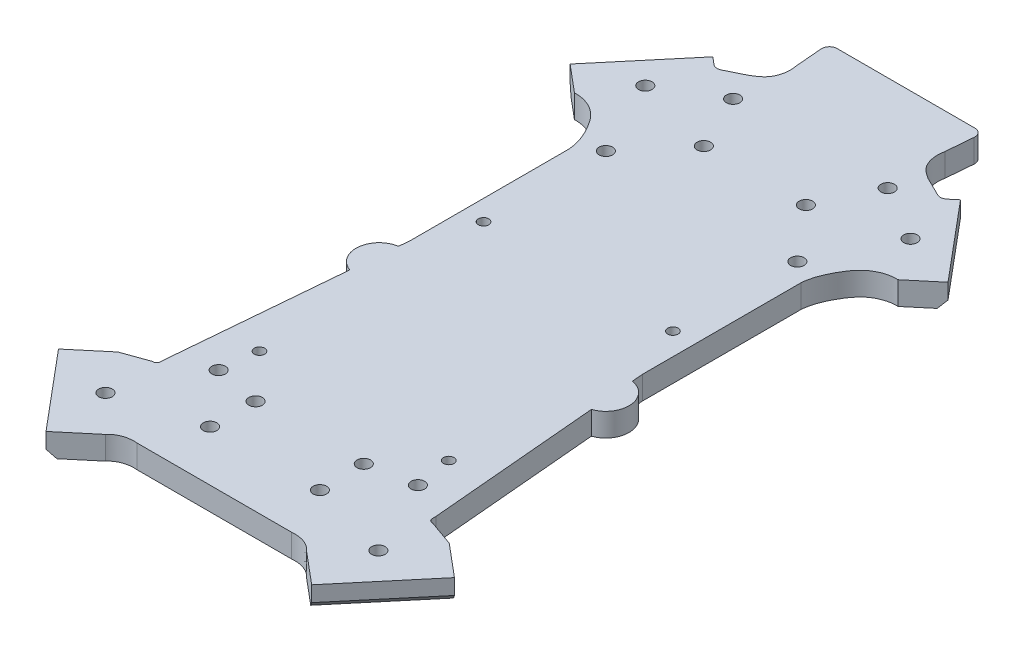
SolidWorks part; units mm, degrees
ref_plane "Front Plane" through (0, 0, 0) normal (0, 0, 1) x (1, 0, 0)
ref_plane "Top Plane" through (0, 0, 0) normal (0, 1, 0) x (1, 0, 0)
ref_plane "Right Plane" through (0, 0, 0) normal (1, 0, 0) x (0, 0, -1)
sketch "Sketch1" plane through (0, 0, 0) normal (0, 1, 0) x (1, 0, 0)
  line L1 (0, 0) -> (200, 0)
  line L2 (0, 0) -> (0, 200)
  line L3 (0, 200) -> (200, 200)
  line L4 (200, 0) -> (200, 200)
  dimension "D1" = 200
  dimension "D2" = 200
extrude "Boss-Extrude1" add sketch "Sketch1" along normal blind 6
sketch "Sketch2" plane through (0, 0, 0) normal (0, -1, 0) x (1, 0, 0)
  line L0 (143.2063, -38.4743) -> (139.3486, -82.5678)
  line L2 (138.3335, -94.1709) -> (138.0819, -97.0459)
  line L3 (138.0819, -97.0459) -> (138.0819, -138.1223)
  line L5 (128.0819, -16.2435) -> (88.0819, -16.2435)
  line L8 (72.9576, -38.4743) -> (76.8153, -82.5678)
  line L10 (77.8304, -94.1709) -> (78.0819, -97.0459)
  line L11 (78.0819, -97.0459) -> (78.0819, -138.1223)
  line L12 (136.0689, -175.4633) -> (131.2216, -177.8581)
  line L14 (127.295, -186.0703) -> (127.8892, -193.0744)
  line L15 (125.8964, -195.2435) -> (90.2675, -195.2435)
  line L16 (108.0819, -195.2435) -> (108.0819, -160.9159) construction
  line L17 (88.8688, -186.0703) -> (88.2746, -193.0744)
  line L18 (80.095, -175.4633) -> (84.9422, -177.8581)
  line L21 (71.8743, -36.5483) -> (65.2141, -34.1729)
  line L22 (65.2141, -34.1729) -> (56.8447, -27.1502)
  line L23 (56.8447, -27.1502) -> (73.7024, -7.0599)
  line L25 (73.7024, -7.0599) -> (82.0719, -14.0827)
  line L30 (66.2141, -151.3141) -> (63.7367, -153.3929)
  line L32 (63.7367, -153.3929) -> (59.1776, -157.2184)
  line L33 (59.1776, -157.2184) -> (76.0353, -177.3087)
  line L35 (76.0353, -177.3087) -> (77.9235, -175.7243)
  line L37 (142.4614, -7.0599) -> (134.092, -14.0827)
  line L38 (159.3191, -27.1502) -> (142.4614, -7.0599)
  line L39 (150.9497, -34.1729) -> (159.3191, -27.1502)
  line L40 (144.2896, -36.5483) -> (150.9497, -34.1729)
  line L45 (149.9497, -151.3141) -> (152.4271, -153.3929)
  line L46 (152.4271, -153.3929) -> (156.9863, -157.2184)
  line L47 (156.9863, -157.2184) -> (140.1285, -177.3087)
  line L48 (140.1285, -177.3087) -> (138.2403, -175.7243)
  line L49 (0, 0) -> (0, -200)
  line L50 (200, 0) -> (0, 0)
  line L51 (200, -200) -> (200, 0)
  line L52 (0, -200) -> (200, -200)
  arc A0 (138.3335, -94.1709) -> (139.3486, -82.5678) centre (137.4028, -88.2435) ccw
  arc A1 (76.8153, -82.5678) -> (77.8304, -94.1709) centre (78.761, -88.2435) ccw
  arc A2 (90.2675, -195.2435) -> (88.2746, -193.0744) centre (90.2675, -193.2435) cw
  arc A3 (127.8892, -193.0744) -> (125.8964, -195.2435) centre (125.8964, -193.2435) cw
  arc A4 (136.0689, -175.4633) -> (138.2403, -175.7243) centre (136.9547, -177.2564) cw
  arc A5 (80.095, -175.4633) -> (77.9235, -175.7243) centre (79.2091, -177.2564) ccw
  spline S2 degree 3 poles (131.2216, -177.8581) (130.2903, -178.4486) (127.4099, -180.2573) (126.8726, -184.0516) (127.295, -186.0703) knots 0 0 0 0 0.342841 1 1 1 1
  spline S3 degree 3 poles (84.9422, -177.8581) (85.8735, -178.4486) (88.754, -180.2573) (89.2912, -184.0516) (88.8688, -186.0703) knots 0 0 0 0 0.342841 1 1 1 1
  spline S6 degree 3 poles (134.092, -14.0827) (132.6324, -15.7971) (130.2548, -16.4555) (128.0819, -16.2435) knots 0 0 0 0 1 1 1 1
  spline S7 degree 3 poles (82.0719, -14.0827) (83.5315, -15.7971) (85.9091, -16.4555) (88.0819, -16.2435) knots 0 0 0 0 1 1 1 1
  spline S8 degree 3 poles (71.8743, -36.5483) (73.0299, -36.4607) (72.9809, -37.7548) (72.9576, -38.4743) knots 0 0 0 0 1 1 1 1
  spline S9 degree 3 poles (144.2896, -36.5483) (143.1339, -36.4607) (143.1829, -37.7548) (143.2063, -38.4743) knots 0 0 0 0 1 1 1 1
  spline S10 degree 3 poles (138.0819, -138.1223) (138.279, -140.6987) (139.8757, -144.4578) (142.8577, -148.8728) (146.318, -150.9496) (148.7119, -151.3752) (149.9497, -151.3141) knots 0 0 0 0 0.390118 0.632218 0.808161 1 1 1 1
  spline S11 degree 3 poles (78.0819, -138.1223) (77.8849, -140.6987) (76.2881, -144.4578) (73.3061, -148.8728) (69.8459, -150.9496) (67.4519, -151.3752) (66.2141, -151.3141) knots 0 0 0 0 0.390118 0.632218 0.808161 1 1 1 1
  point P90 (147.6197, -35.3606)
  point P104 (128.0733, -195.2435)
extrude "Cut-Extrude2" cut sketch "Sketch2" against normal through all both and the other way through all
hole_wizard "Ø3.0mm Dowel Hole1" positions "Sketch4" profile "Sketch5" hole size "Ø3.0" standard "ANSI Metric" end condition through all
sketch "Sketch4" plane through (0, 0, 0) normal (0, -1, 0) x (-1, 0, 0)
  point P0 (-83.2968, 142.3491)
  point P3 (-94.867, 156.1379)
  point P6 (-121.2968, 156.1379)
  point P9 (-132.867, 142.3491)
  point P12 (-128.0819, 170.5038)
  point P15 (-142.4028, 162.0993)
  point P18 (-88.0819, 170.5038)
  point P21 (-73.761, 162.0993)
  point P24 (-133.867, 43.1379)
  point P27 (-122.0819, 40.922)
  point P30 (-122.2968, 29.3491)
  point P33 (-94.0819, 40.922)
  point P36 (-93.867, 29.3491)
  point P39 (-82.2968, 43.1379)
  point P42 (-72.761, 23.3877)
  point P45 (-143.4028, 23.3877)
sketch "Sketch5" plane through (83.2968, 0, -142.3491) normal (1, 0, 0) x (0, 0, -1)
  line L0 (0, 0) -> (0, 6)
  line L1 (0, 6) -> (1.75, 6)
  line L2 (1.75, 6) -> (1.75, 0)
  line L5 (1.75, 0) -> (0, 0)
  line L11 (0, -6.35) -> (0, 107.95) construction
  dimension "Thru Hole Dia." = 3.5
  dimension "Thru Hole Depth" = 6
sketch "Sketch6" plane through (0, 0, 0) normal (0, -1, 0) x (1, 0, 0)
  line L0 (125.0968, -27.7325) -> (122.2968, -26.1159)
  line L1 (122.2968, -26.1159) -> (119.4968, -27.7325)
  line L2 (119.4968, -27.7325) -> (119.4968, -30.9657)
  line L5 (119.4968, -30.9657) -> (122.2968, -32.5823)
  line L6 (122.2968, -32.5823) -> (125.0968, -30.9657)
  line L7 (125.0968, -30.9657) -> (125.0968, -27.7325)
  line L8 (133.867, -39.9047) -> (131.067, -41.5213)
  line L9 (131.067, -41.5213) -> (131.067, -44.7545)
  line L10 (131.067, -44.7545) -> (133.867, -46.3711)
  line L11 (133.867, -46.3711) -> (136.667, -44.7545)
  line L12 (136.667, -44.7545) -> (136.667, -41.5213)
  line L13 (136.667, -41.5213) -> (133.867, -39.9047)
  line L22 (82.2968, -39.9047) -> (79.4968, -41.5213)
  line L23 (79.4968, -41.5213) -> (79.4968, -44.7545)
  line L24 (79.4968, -44.7545) -> (82.2968, -46.3711)
  line L26 (82.2968, -46.3711) -> (85.0968, -44.7545)
  line L27 (85.0968, -44.7545) -> (85.0968, -41.5213)
  line L30 (85.0968, -41.5213) -> (82.2968, -39.9047)
  line L31 (93.867, -26.1159) -> (91.067, -27.7325)
  line L34 (91.067, -27.7325) -> (91.067, -30.9657)
  line L36 (91.067, -30.9657) -> (93.867, -32.5823)
  line L37 (93.867, -32.5823) -> (96.667, -30.9657)
  line L38 (96.667, -30.9657) -> (96.667, -27.7325)
  line L39 (96.667, -27.7325) -> (93.867, -26.1159)
  line L40 (94.867, -152.9047) -> (92.067, -154.5213)
  line L41 (92.067, -154.5213) -> (92.067, -157.7545)
  line L42 (92.067, -157.7545) -> (94.867, -159.3711)
  line L43 (94.867, -159.3711) -> (97.667, -157.7545)
  line L44 (97.667, -157.7545) -> (97.667, -154.5213)
  line L45 (97.667, -154.5213) -> (94.867, -152.9047)
  line L46 (83.2968, -139.1159) -> (80.4968, -140.7325)
  line L47 (80.4968, -140.7325) -> (80.4968, -143.9657)
  line L48 (80.4968, -143.9657) -> (83.2968, -145.5823)
  line L49 (83.2968, -145.5823) -> (86.0968, -143.9657)
  line L50 (86.0968, -143.9657) -> (86.0968, -140.7325)
  line L51 (86.0968, -140.7325) -> (83.2968, -139.1159)
  line L52 (121.2968, -152.9047) -> (118.4968, -154.5213)
  line L53 (118.4968, -154.5213) -> (118.4968, -157.7545)
  line L54 (118.4968, -157.7545) -> (121.2968, -159.3711)
  line L55 (121.2968, -159.3711) -> (124.0968, -157.7545)
  line L56 (124.0968, -157.7545) -> (124.0968, -154.5213)
  line L57 (124.0968, -154.5213) -> (121.2968, -152.9047)
  line L58 (132.867, -145.5823) -> (135.667, -143.9657)
  line L59 (135.667, -143.9657) -> (135.667, -140.7325)
  line L60 (135.667, -140.7325) -> (132.867, -139.1159)
  line L61 (132.867, -139.1159) -> (130.067, -140.7325)
  line L62 (130.067, -140.7325) -> (130.067, -143.9657)
  line L63 (130.067, -143.9657) -> (132.867, -145.5823)
extrude "Cut-Extrude3" cut sketch "Sketch6" against normal blind 2.2
sketch "Sketch7" plane through (0, 0, 0) normal (0, -1, 0) x (-1, 0, 0)
  circle A0 centre (-83.3425, 52.6603) radius 1.35
  circle A1 centre (-132.3425, 52.6603) radius 1.35
  circle A2 centre (-83.3425, 110.6603) radius 1.35
  circle A3 centre (-132.3425, 110.6603) radius 1.35
extrude "Cut-Extrude4" cut sketch "Sketch7" along normal through all both and the other way through all
chamfer "Chamfer2" distance 2 angle 45 4 edges at (148.5574, 0, -167.2636) (67.6064, 0, -167.2636) (65.2736, 0, -17.105) (150.8903, 0, -17.105)
